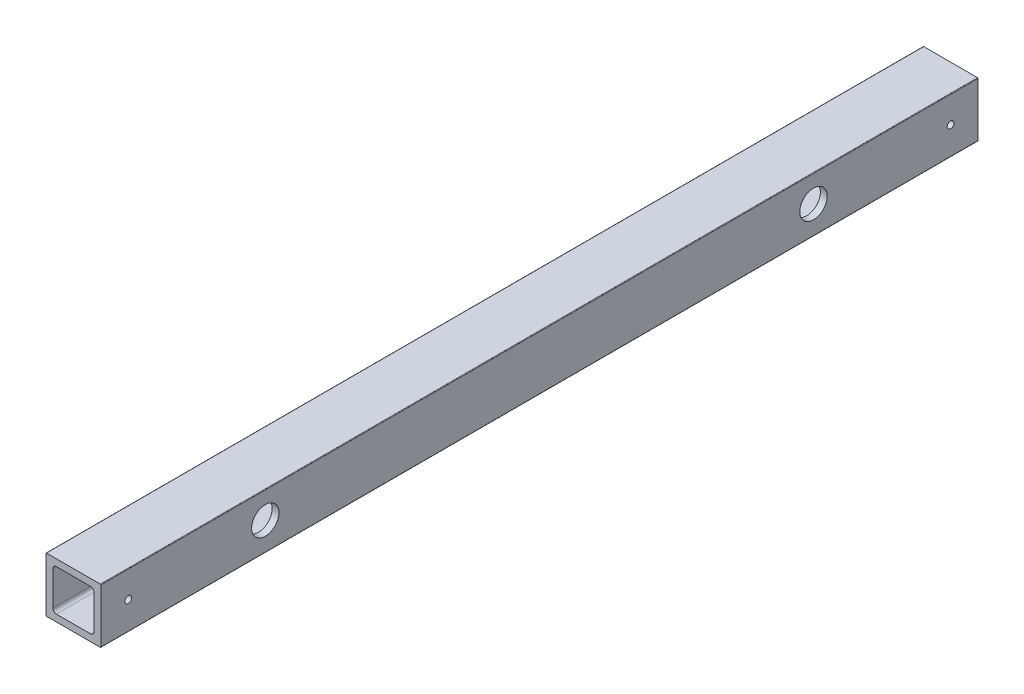
SolidWorks part; units mm, degrees
ref_plane "Front Plane" through (0, 0, 0) normal (0, 0, 1) x (1, 0, 0)
ref_plane "Top Plane" through (0, 0, 0) normal (0, 1, 0) x (1, 0, 0)
ref_plane "Right Plane" through (0, 0, 0) normal (1, 0, 0) x (0, 0, -1)
ref_plane "Plane1" through (0, 0, 0) normal (0, 0, -1) x (-1, 0, 0)
sketch "Sketch1" plane through (0, 0, 0) normal (0, 0, -1) x (-1, 0, 0)
  line L0 (-3.175, 20.6375) -> (-3.175, 4.7625)
  line L1 (-4.7625, 3.175) -> (-20.6375, 3.175)
  line L2 (-22.225, 4.7625) -> (-22.225, 20.6375)
  line L3 (-20.6375, 22.225) -> (-4.7625, 22.225)
  line L4 (0, 0.254) -> (0, 25.146)
  line L5 (-0.254, 25.4) -> (-25.146, 25.4)
  line L6 (-25.4, 25.146) -> (-25.4, 0.254)
  line L7 (-25.146, 0) -> (-0.254, 0)
  arc A0 (-3.175, 4.7625) -> (-4.7625, 3.175) centre (-4.7625, 4.7625) cw
  arc A1 (-20.6375, 3.175) -> (-22.225, 4.7625) centre (-20.6375, 4.7625) cw
  arc A2 (-22.225, 20.6375) -> (-20.6375, 22.225) centre (-20.6375, 20.6375) cw
  arc A3 (-4.7625, 22.225) -> (-3.175, 20.6375) centre (-4.7625, 20.6375) cw
  arc A4 (-0.254, 0) -> (0, 0.254) centre (-0.254, 0.254) ccw
  arc A5 (0, 25.146) -> (-0.254, 25.4) centre (-0.254, 25.146) ccw
  arc A6 (-25.146, 25.4) -> (-25.4, 25.146) centre (-25.146, 25.146) ccw
  arc A7 (-25.4, 0.254) -> (-25.146, 0) centre (-25.146, 0.254) ccw
  dimension "D1" = 25.4
  dimension "D2" = 25.4
  dimension "D3" = 19.05
  dimension "D4" = 3.175
  dimension "D5" = 19.05
extrude "Boss-Extrude1" add sketch "Sketch1" against normal blind 406.4
sketch "Sketch2" plane through (0, 0, 0) normal (-1, 0, 0) x (0, 0, 1)
  line L0 (0, 0.254) -> (0, 25.146) construction
  line L1 (406.4, 0.254) -> (0, 0.254) construction
  line L2 (406.4, 0.254) -> (406.4, 25.146) construction
  circle A0 centre (12.6975, 12.954) radius 1.5875
  circle A1 centre (393.7, 12.954) radius 1.5875
  circle A2 centre (76.2, 12.954) radius 6.35
  circle A3 centre (330.2, 12.954) radius 6.35
  point P4 (0, 12.7)
  dimension "D1" = 3.175
  dimension "D2" = 12.7
  dimension "D3" = 12.7
  dimension "D4" = 3.175
  dimension "D5" = 12.7
  dimension "D6" = 12.7
  dimension "D7" = 12.7
  dimension "D8" = 12.7
  dimension "D9" = 76.2
  dimension "D10" = 12.7
  dimension "D11" = 12.7
  dimension "D12" = 76.2
extrude "Cut-Extrude1" cut sketch "Sketch2" against normal through all
